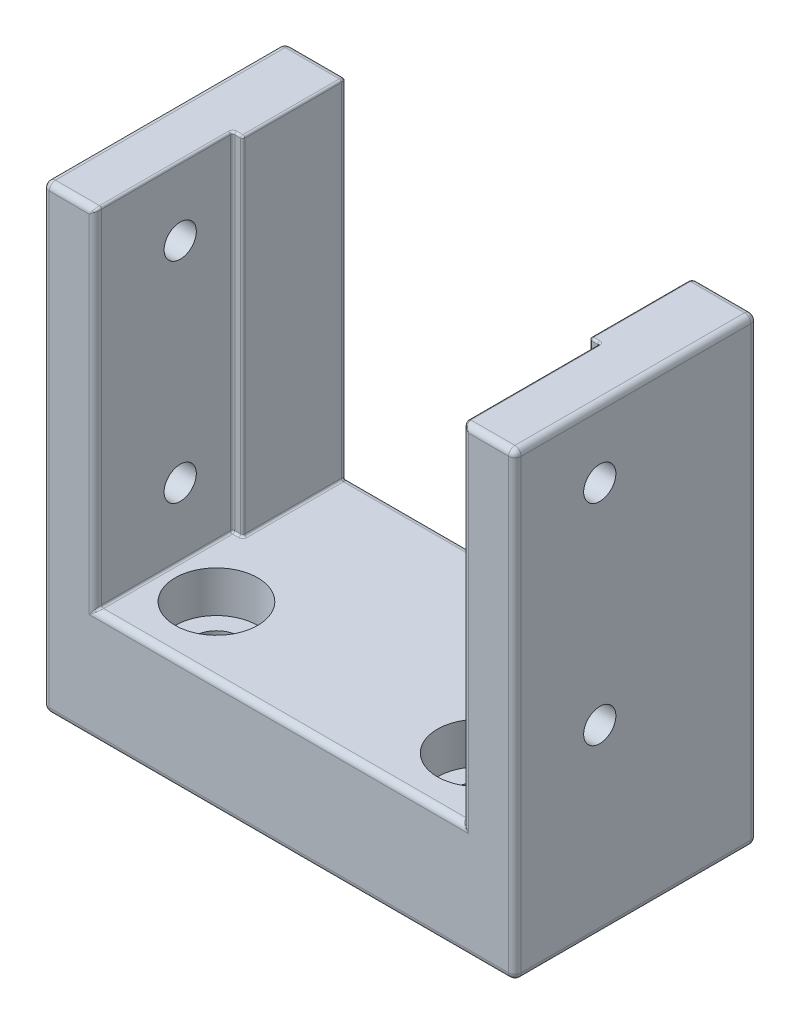
SolidWorks part; units mm, degrees
material "PLA"
ref_plane "Front Plane" through (0, 0, 0) normal (0, 0, 1) x (1, 0, 0)
ref_plane "Top Plane" through (0, 0, 0) normal (0, 1, 0) x (1, 0, 0)
ref_plane "Right Plane" through (0, 0, 0) normal (1, 0, 0) x (0, 0, -1)
sketch "Sketch1" plane through (0, 0, 0) normal (0, 1, 0) x (1, 0, 0)
  line L1 (-22.225, 14.6625) -> (22.225, 14.6625)
  line L2 (-22.225, 14.6625) -> (-22.225, -14.6625)
  line L3 (-22.225, -14.6625) -> (22.225, -14.6625)
  line L4 (22.225, 14.6625) -> (22.225, -14.6625)
  point P4 (0, -14.6625)
  point P6 (-22.225, 0)
  dimension "D1" = 29.325
  dimension "D2" = 44.45
extrude "Boss-Extrude1" add sketch "Sketch1" against normal blind 13.685
sketch "Sketch2" plane through (22.225, 0, 0) normal (1, 0, 0) x (0, 0, -1)
  line L0 (14.6625, -13.685) -> (14.6625, 0) construction
  line L1 (-14.6625, -13.685) -> (14.6625, -13.685)
  line L2 (-14.6625, -13.685) -> (-14.6625, 42)
  line L3 (-14.6625, 42) -> (14.6625, 42)
  line L4 (14.6625, -13.685) -> (14.6625, 42)
  point P5 (-4.3875, 33.7)
  point P6 (-4.3875, 8.3)
  dimension "D1" = 55.685
extrude "Boss-Extrude2" add sketch "Sketch2" along normal blind 6.35
hole_wizard "M3.5 Clearance Hole1" positions "Sketch5" profile "Sketch6" hole size "M3.5" standard "ANSI Metric" end condition through all
sketch "Sketch5" plane through (28.575, 0, 0) normal (1, 0, 0) x (0, 0, -1)
  line L1 (14.6625, 42) -> (-14.6625, 42) construction
  line L2 (-14.6625, 42) -> (-14.6625, -13.685) construction
  point P0 (-4.3875, 33.7)
  point P2 (-4.3875, 8.3)
  dimension "D1" = 10.275
  dimension "D2" = 8.3
  dimension "D3" = 25.4
sketch "Sketch6" plane through (28.575, 33.7, 4.3875) normal (0, 1, 0) x (0, 0, -1)
  line L0 (0, 0) -> (0, 50.8)
  line L1 (0, 50.8) -> (1.95, 50.8)
  line L2 (1.95, 50.8) -> (1.95, 0)
  line L5 (1.95, 0) -> (0, 0)
  line L11 (0, -6.35) -> (0, 107.95) construction
  dimension "Thru Hole Dia." = 3.9
  dimension "Thru Hole Depth" = 50.8
mirror "Mirror1" about plane through (0, 0, 0) normal (1, 0, 0) of "Boss-Extrude2", "M3.5 Clearance Hole1"
sketch "Sketch8" plane through (22.225, 0, 0) normal (-1, 0, 0) x (0, 0, 1)
  line L0 (-14.6625, 42) -> (14.6625, 42) construction
  line L1 (-14.6625, 0) -> (-1.9625, 0)
  line L2 (-14.6625, 0) -> (-14.6625, 42)
  line L3 (-14.6625, 42) -> (-1.9625, 42)
  line L4 (-1.9625, 0) -> (-1.9625, 42)
  dimension "D1" = 12.7
extrude "Boss-Extrude6" add sketch "Sketch8" along normal blind 1.225
mirror "Mirror2" about plane through (0, 0, 0) normal (1, 0, 0) of "Boss-Extrude6"
hole_wizard "CBORE for M5 SHCS1" positions "Sketch9" profile "Sketch10" counterbore size "M5" standard "ANSI Metric" end condition through all
sketch "Sketch9" plane through (0, 0, 0) normal (0, 1, 0) x (1, 0, 0)
  line L0 (-22.225, 1.9625) -> (-22.225, -14.6625) construction
  line L1 (0, -16.1288) -> (0, 16.1288) construction
  point P0 (15.875, -6.35)
  point P2 (-15.875, -6.35)
  point P8 (-22.225, -6.35)
  dimension "D1" = 15.875
  dimension "D2" = 15.875
sketch "Sketch10" plane through (15.875, 0, 6.35) normal (1, 0, 0) x (0, 0, 1)
  line L0 (0, 0) -> (0, 13.685)
  line L1 (0, 13.685) -> (2.75, 13.685)
  line L3 (2.75, 13.685) -> (2.75, 5)
  line L4 (2.75, 5) -> (5, 5)
  line L5 (5, 5) -> (5, 0)
  line L7 (5, 0) -> (0, 0)
  line L11 (0, -6.35) -> (0, 107.95) construction
  dimension "Thru Hole Dia." = 5.5
  dimension "Thru Hole Depth" = 13.685
  dimension "C'Bore Dia." = 10
  dimension "C'Bore Depth" = 5
fillet "Fillet1" radius 0.762 22 edges at (-21, 21, -14.6625) (-24.7875, 42, -14.6625) (-28.575, 14.1575, -14.6625) (28.575, 14.1575, -14.6625) (24.7875, 42, -14.6625) (21, 21, -14.6625) (0, 0, -14.6625) (22.225, 21, 14.6625) (25.4, 42, 14.6625) (28.575, 14.1575, 14.6625) (-28.575, 14.1575, 14.6625) (-25.4, 42, 14.6625) (-22.225, 21, 14.6625) (0, 0, 14.6625) (28.575, -13.685, 0) (0, -13.685, -14.6625) (-28.575, -13.685, 0) (0, -13.685, 14.6625) (-15.875, -13.685, 9.1) (15.875, -13.685, 9.1) (28.575, 42, 0) (-28.575, 42, 0)
fillet "Fillet2" radius 0.254 24 edges at (-21.2232, -0.2232, -14.4393) (21.2232, -0.2232, -14.4393) (22.4482, 41.7768, 14.4393) (-21, 0, -7.9315) (21, 0, -7.9315) (22.225, 42, 5.969) (-22.4482, -0.2232, 14.4393) (-21.2232, 41.7768, -14.4393) (-22.4482, 41.7768, 14.4393) (22.4482, -0.2232, 14.4393) (21.2232, 41.7768, -14.4393) (-22.225, 0, 5.969) (-21.6125, 0, -1.9625) (-21, 42, -7.9315) (-21, 21, -1.9625) (-22.225, 21, -1.9625) (-21.6125, 42, -1.9625) (-22.225, 42, 5.969) (21.6125, 0, -1.9625) (22.225, 0, 5.969) (21.6125, 42, -1.9625) (21, 21, -1.9625) (22.225, 21, -1.9625) (21, 42, -7.9315)
